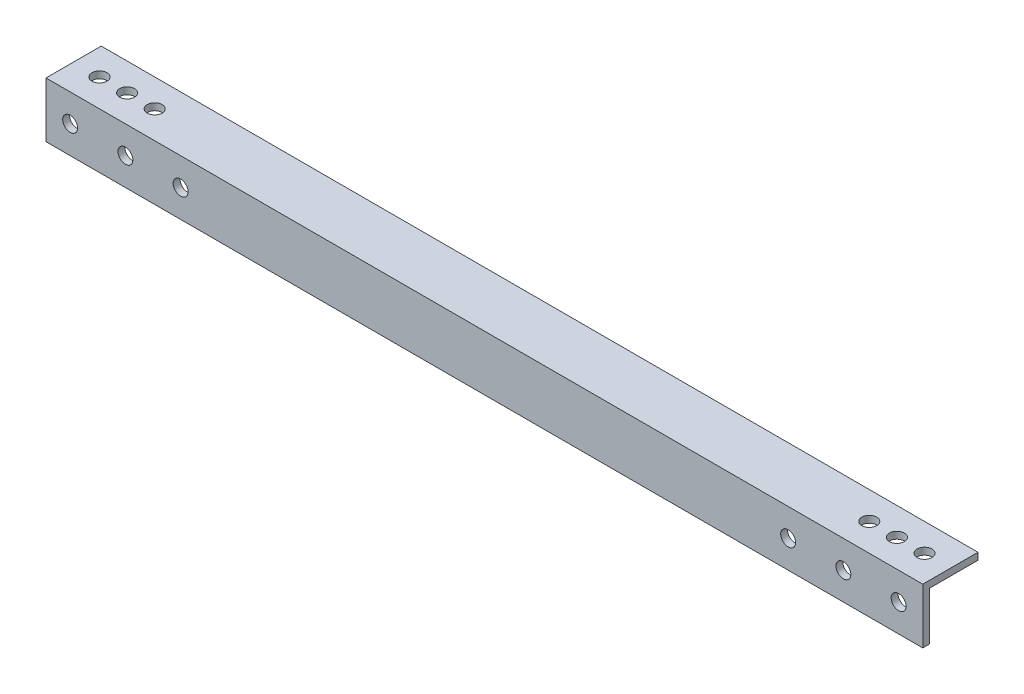
SolidWorks part; units mm, degrees
ref_plane "Front Plane" through (0, 0, 0) normal (0, 0, 1) x (1, 0, 0)
ref_plane "Top Plane" through (0, 0, 0) normal (0, 1, 0) x (1, 0, 0)
ref_plane "Right Plane" through (0, 0, 0) normal (1, 0, 0) x (0, 0, -1)
sketch "Sketch1" plane through (0, 0, 0) normal (1, 0, 0) x (0, 0, -1)
  line L0 (0, 0) -> (25.4, 0)
  line L2 (0, 0) -> (0, -25.4)
  line L4 (3.175, -3.175) -> (25.4, -3.175)
  line L5 (3.175, -3.175) -> (3.175, -25.4)
  line L6 (25.4, -3.175) -> (25.4, 0)
  line L7 (3.175, -25.4) -> (0, -25.4)
  line L8 (55, 0) -> (-55, 0) construction
  line L9 (0, 55) -> (0, -55) construction
  point P0 (3.175, -25.4)
  dimension "D1" = 25.4
  dimension "D2" = 25.4
  dimension "D4" = 3.175
  dimension "D3" = 3.175
extrude "Boss-Extrude1" add sketch "Sketch1" along normal blind 403.225
sketch "Sketch2" plane through (0, 0, 0) normal (0, 0, 1) x (1, 0, 0)
  line L0 (0, -12.7) -> (61.9125, -12.7) construction
  line L1 (0, -55) -> (0, 55) construction
  line L2 (403.225, -25.4) -> (0, -25.4) construction
  line L3 (0, 0) -> (0, -25.4) construction
  line L4 (201.6125, -25.4) -> (201.6125, 0) construction
  line L6 (403.225, 0) -> (0, 0) construction
  line L7 (403.225, -12.7) -> (341.3125, -12.7) construction
  circle A0 centre (11.1125, -12.7) radius 3.429
  circle A1 centre (36.5125, -12.7) radius 3.429
  circle A2 centre (61.9125, -12.7) radius 3.429
  circle A3 centre (341.3125, -12.7) radius 3.429
  circle A4 centre (366.7125, -12.7) radius 3.429
  circle A5 centre (392.1125, -12.7) radius 3.429
  point P13 (0, 0)
  point P18 (0, 0)
  dimension "D1" = 12.7
  dimension "D2" = 6.858
  dimension "D3" = 11.1125
  dimension "D5" = 25.4
  dimension "D4" = 3
extrude "Cut-Extrude1" cut sketch "Sketch2" against normal up to surface (3.175 mm away) up to face at (201.6125, -14.2875, -3.175)
sketch "Sketch3" plane through (0, 0, 0) normal (0, 1, 0) x (1, 0, 0)
  line L1 (0, -55) -> (0, 55) construction
  line L4 (201.6125, 25.4) -> (201.6125, 0) construction
  line L5 (403.225, 25.4) -> (0, 25.4) construction
  line L6 (403.225, 0) -> (0, 0) construction
  circle A0 centre (11.8999, 12.7) radius 3.429
  circle A1 centre (24.5999, 12.7) radius 3.429
  circle A2 centre (37.2999, 12.7) radius 3.429
  circle A3 centre (365.9251, 12.7) radius 3.429
  circle A4 centre (378.6251, 12.7) radius 3.429
  circle A5 centre (391.3251, 12.7) radius 3.429
  dimension "D1" = 6.858
  dimension "D2" = 11.8999
  dimension "D5" = 12.7
  dimension "D4" = 12.7
  dimension "D3" = 3
extrude "Cut-Extrude2" cut sketch "Sketch3" against normal up to surface (3.175 mm away) up to face at (201.6125, -3.175, -14.2875)
